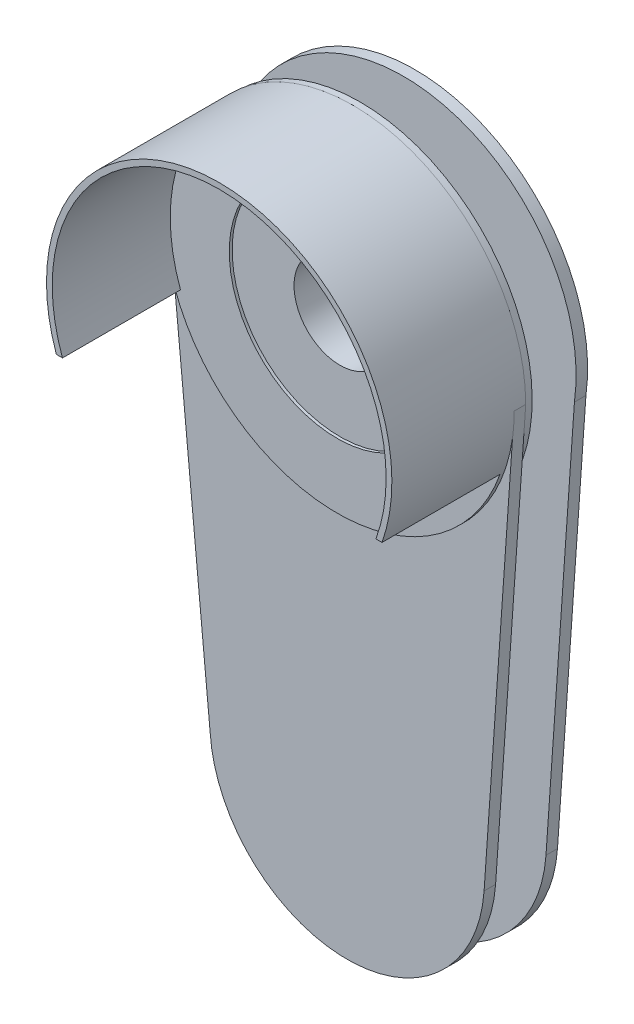
SolidWorks part; units mm, degrees
other "Markup1"
sketch "Sketch21" plane through (-120, -388.0087, 85) normal (-0.6286, -0.5768, 0.5217) x (0.2924, 0.4463, 0.8458)
ref_plane "Front Plane" through (0, 0, 0) normal (0, 0, 1) x (1, 0, 0)
ref_plane "Top Plane" through (0, 0, 0) normal (0, 1, 0) x (1, 0, 0)
ref_plane "Right Plane" through (0, 0, 0) normal (1, 0, 0) x (0, 0, -1)
sketch "Sketch2" plane through (0, 0, 0) normal (0, 0, 1) x (1, 0, 0)
  circle A0 centre (0, 0) radius 120
extrude "Boss-Extrude2" add sketch "Sketch2" along normal blind 85
sketch "Sketch3" plane through (0, 0, 85) normal (0, 0, 1) x (1, 0, 0)
  line L0 (-113.1371, -40) -> (-108.8853, -40)
  line L1 (108.8853, -40) -> (113.1371, -40)
  arc A0 (108.8853, -40) -> (-108.8853, -40) centre (0, 0) ccw
  arc A1 (113.1371, -40) -> (-113.1371, -40) centre (0, 0) ccw
  circle M1 centre (0, 0) radius 120
  dimension "D1" = 40
extrude "Cut-Extrude1" cut sketch "Sketch3" against normal blind 82 contours L1 A0 L0 M1 region at (0, -2.4133, 85)
sketch "Sketch8" plane through (0, 0, 3) normal (0, 0, 1) x (1, 0, 0)
  circle A0 centre (0, 0) radius 75
extrude "Cut-Extrude5" cut sketch "Sketch8" along normal blind 2 and the other way blind 2
sketch "Sketch9" plane through (0, 0, 1) normal (0, 0, 1) x (1, 0, 0)
  line L0 (0, 0) -> (-75, 0) construction
  line L1 (0, 0) -> (0, 75) construction
  circle A0 centre (0, 0) radius 75 construction
  circle A1 centre (0, 0) radius 32
extrude "Cut-Extrude6" cut sketch "Sketch9" against normal blind 5 contours A1
sketch "Sketch12" plane through (0, 0, 0) normal (0, 0, -1) x (-1, 0, 0)
  line L0 (-120, 0) -> (-99.0634, -299.2685)
  line L1 (120, 0) -> (91.3099, -298.625)
  circle A1 centre (0, 0) radius 120 construction
  arc A2 (-99.0634, -299.2685) -> (91.3099, -298.625) centre (-3.8981, -292.6108) ccw
  circle A3 centre (0, 0) radius 120
  circle M3 centre (0, 0) radius 32
  circle M4 centre (0, 0) radius 120
extrude "Boss-Extrude4" add sketch "Sketch12" along normal blind 8 contours L1 L0 M4 M3 | L0 A2 L1 M4 region at (0, 116.6059, 0) region at (3.1223, -228.039, 0)
sketch "Sketch13" plane through (0, 0, -8) normal (0, 0, -1) x (-1, 0, 0)
  circle A0 centre (0, 0) radius 119.4702
extrude "Boss-Extrude5" add sketch "Sketch13" along normal blind 5
sketch "Sketch15" plane through (0, 0, -13) normal (0, 0, -1) x (-1, 0, 0)
  circle A0 centre (0, 0) radius 70
extrude "Boss-Extrude6" add sketch "Sketch15" along normal blind 30
sketch "Sketch16" plane through (0, 0, -43) normal (0, 0, -1) x (-1, 0, 0)
  circle A0 centre (0, 0) radius 120
extrude "Boss-Extrude7" add sketch "Sketch16" along normal blind 8
sketch "Sketch19" plane through (0, 0, -51) normal (0, 0, -1) x (-1, 0, 0)
  circle A0 centre (0, 0) radius 32
extrude "Cut-Extrude7" cut sketch "Sketch19" against normal blind 210
sketch "Sketch20" plane through (0, 0, -51) normal (0, 0, -1) x (-1, 0, 0)
  line L0 (-120, 0) -> (-99.0634, -299.2685)
  line L1 (91.3099, -298.625) -> (120, 0)
  line L5 (119.1128, -9.2343) -> (120, 0)
  line L6 (-120, 0) -> (-99.0634, -299.2685)
  line L7 (91.3099, -298.625) -> (118.6922, -13.6125)
  line L8 (119.1128, -9.2343) -> (120, 0)
  line L9 (-120, 0) -> (-99.0634, -299.2685)
  line L10 (91.3099, -298.625) -> (118.6922, -13.6125)
  arc A0 (-99.0634, -299.2685) -> (91.3099, -298.625) centre (-3.8981, -292.6108) ccw
  arc A4 (119.1128, -9.2343) -> (118.6922, -13.6125) centre (0, 0) ccw
  arc A5 (120, 0) -> (-120, 0) centre (0, 0) ccw
  arc A6 (-99.0634, -299.2685) -> (91.3099, -298.625) centre (-3.8981, -292.6108) ccw
  arc A7 (119.1128, -9.2343) -> (118.6922, -13.6125) centre (0, 0) ccw
  arc A9 (-99.0634, -299.2685) -> (91.3099, -298.625) centre (-3.8981, -292.6108) ccw
  circle M2 centre (0, 0) radius 120
  dimension "D1" = 0
extrude "Boss-Extrude8" add sketch "Sketch20" against normal blind 8 contours L0 A0 L1 M2 region at (3.1223, -228.039, -51)
